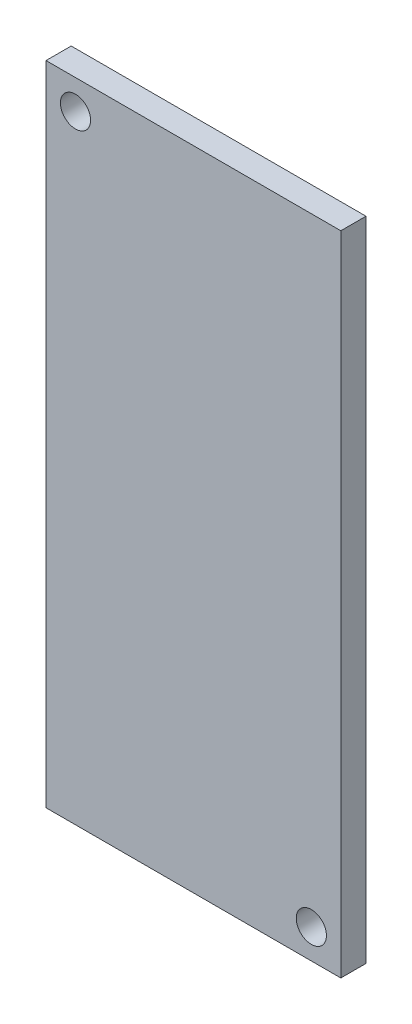
SolidWorks part; units mm, degrees
ref_plane "Front Plane" through (0, 0, 0) normal (0, 0, 1) x (1, 0, 0)
ref_plane "Top Plane" through (0, 0, 0) normal (0, 1, 0) x (1, 0, 0)
ref_plane "Right Plane" through (0, 0, 0) normal (1, 0, 0) x (0, 0, -1)
sketch "Sketch1" plane through (0, 0, 0) normal (0, 0, 1) x (1, 0, 0)
  line L0 (10.25, 0) -> (-10.25, 0) construction
  line L1 (-10.25, 22.5) -> (10.25, 22.5)
  line L2 (-10.25, 22.5) -> (-10.25, -22.5)
  line L3 (-10.25, -22.5) -> (10.25, -22.5)
  line L4 (10.25, 22.5) -> (10.25, -22.5)
  dimension "D1" = 20.5
  dimension "D2" = 45
extrude "Extrude1" add sketch "Sketch1" along normal blind 1.75
sketch "Sketch2" plane through (0, 0, 1.75) normal (0, 0, 1) x (1, 0, 0)
  line L0 (-10.25, -22.5) -> (10.25, -22.5) construction
  line L1 (-10.25, 22.5) -> (-10.25, -22.5) construction
  line L2 (10.25, 22.5) -> (-10.25, 22.5) construction
  line L3 (10.25, -22.5) -> (10.25, 22.5) construction
  circle A0 centre (8.2, -20.45) radius 1.05
  circle A1 centre (-8.2, 20.45) radius 1.05
  dimension "D1" = 2.1
  dimension "D2" = 2.05
  dimension "D3" = 2.05
  dimension "D4" = 2.1
  dimension "D5" = 1
  dimension "D6" = 2.05
extrude "Cut-Extrude1" cut sketch "Sketch2" against normal up to surface (1.75 mm away) up to face at (0, 0, 0)
